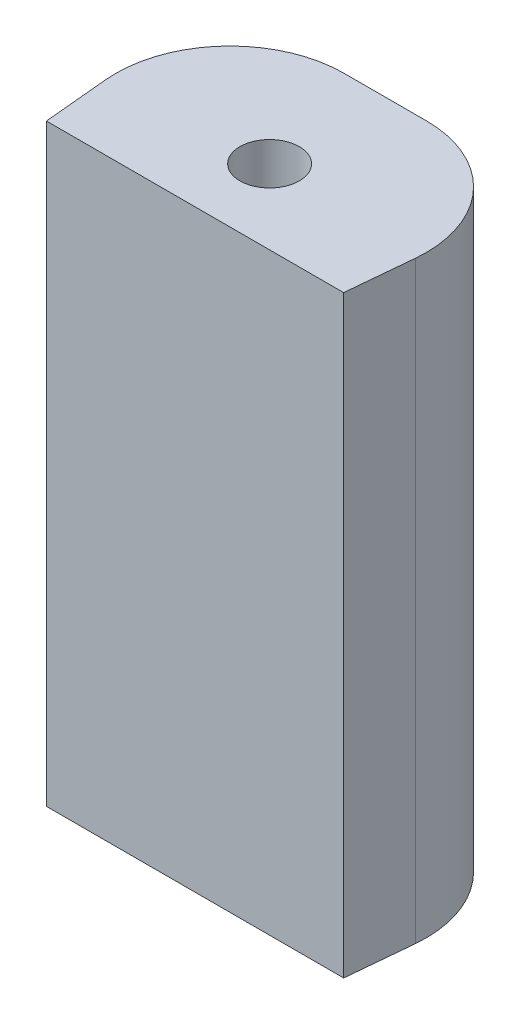
SolidWorks part; units mm, degrees
ref_plane "Front Plane" through (0, 0, 0) normal (0, 0, 1) x (1, 0, 0)
ref_plane "Top Plane" through (0, 0, 0) normal (0, 1, 0) x (1, 0, 0)
ref_plane "Right Plane" through (0, 0, 0) normal (1, 0, 0) x (0, 0, -1)
sketch "Sketch1" plane through (0, 0, 0) normal (0, 1, 0) x (1, 0, 0)
  line L0 (1.1081, 1.7265) -> (-45.0799, 1.7265) construction
  line L1 (-45.0799, 1.7265) -> (-45.0799, -11.2275) construction
  line L2 (-45.0799, -11.2275) -> (43.7517, -11.2275) construction
  line L3 (1.1081, 103.3269) -> (1.1081, -99.8738) construction
  line L4 (-45.0799, -11.2275) -> (-45.0799, -20.7525) construction
  line L5 (-28.2049, 1.7265) -> (-28.2049, -3.6075) construction
  line L6 (-9.9553, -3.6075) -> (-6.7697, -3.6075)
  line L7 (-28.2049, -3.6075) -> (-9.9553, -3.6075) construction
  line L8 (-6.7697, -3.6075) -> (1.1081, -3.6075) construction
  line L9 (8.9859, -3.6075) -> (12.1715, -3.6075)
  line L10 (12.1715, -3.6075) -> (18.1346, -3.6075) construction
  line L11 (12.1715, -3.6075) -> (18.1346, -3.6075) construction
  line L12 (18.1346, -3.6075) -> (29.3788, -3.6075) construction
  line L13 (1.1081, -3.6075) -> (8.9859, -3.6075) construction
  line L14 (-6.7697, -3.6075) -> (8.9859, -3.6075)
  circle A0 centre (1.1081, -11.3265) radius 1.9844 construction
  circle A1 centre (1.1081, -11.3265) radius 1.9844
  spline S0 degree 3 poles (1.1081, -99.8738) (4.5273, -73.5318) (7.9866, -47.1872) (10.6029, -20.7525) knots 0 0 0 0 0.38497 0.38497 0.38497 0.38497
  spline S3 degree 3 poles (1.1081, -99.8738) (-2.3112, -73.5318) (-5.7704, -47.1872) (-8.3867, -20.7525) knots 0 0 0 0 0.38497 0.38497 0.38497 0.38497
  spline S4 degree 3 poles (10.6029, -20.7525) (11.1, -15.7302) (11.6306, -10.016) (12.114, -4.2968) (12.1715, -3.6075) knots 0.38497 0.38497 0.38497 0.38497 0.458109 0.468132 0.468132 0.468132 0.468132
  spline S5 degree 3 poles (-8.3867, -20.7525) (-8.8838, -15.7302) (-9.4144, -10.016) (-9.8978, -4.2968) (-9.9553, -3.6075) knots 0.38497 0.38497 0.38497 0.38497 0.458109 0.468132 0.468132 0.468132 0.468132
  spline S8 degree 3 poles (12.1715, -3.6075) (12.8364, 4.367) (14.1908, 23.6726) (14.0058, 48.0803) (13.0188, 67.5796) (11.3266, 78.9472) (9.5869, 86.9693) (8.1237, 93.6397) (6.4505, 97.563) (4.8164, 101.3994) (2.3437, 102.5279) (1.1081, 103.3269) knots 0.468132 0.468132 0.468132 0.468132 0.584075 0.748482 0.821537 0.866809 0.914778 0.94069 0.965303 0.976863 1 1 1 1 construction
  spline S9 degree 3 poles (1.1081, 99.6196) (1.2739, 99.518) (1.6209, 99.2976) (2.0134, 99.0137) (2.3095, 98.7539) (2.4667, 98.5788) (2.6076, 98.3713) (2.8163, 97.9774) (3.0534, 97.4394) (3.4327, 96.5453) (3.8774, 95.496) (4.541, 93.8448) (5.2023, 91.9048) (5.8236, 89.3366) (6.4213, 86.5662) (7.0145, 83.8293) (7.767, 80.1951) (8.6007, 75.6781) (9.6391, 68.4081) (10.3034, 59.2354) (10.6788, 47.9926) (10.8555, 36.7918) (10.7415, 25.5951) (10.3009, 14.4244) (9.6564, 4.6878) (9.1767, -1.3266) (8.9859, -3.6075) knots 0.118744 0.118744 0.118744 0.118744 0.122149 0.125554 0.12896 0.132365 0.13577 0.139175 0.142581 0.145986 0.152796 0.159607 0.173228 0.186849 0.20047 0.214091 0.227711 0.254953 0.282195 0.336679 0.391163 0.445646 0.50013 0.554614 0.609098 0.642376 0.642376 0.642376 0.642376 construction
  spline S10 degree 3 poles (-7.1984, 1.7265) (-7.237, 2.2289) (-7.5577, 6.4638) (-8.0847, 14.4244) (-8.5253, 25.5951) (-8.6393, 36.7918) (-8.4626, 47.9926) (-8.0872, 59.2354) (-7.4229, 68.4081) (-6.3845, 75.6781) (-5.5508, 80.1951) (-4.7983, 83.8293) (-4.2051, 86.5662) (-3.6074, 89.3366) (-2.9861, 91.9048) (-2.3248, 93.8448) (-1.6612, 95.496) (-1.2165, 96.5453) (-0.8372, 97.4394) (-0.6001, 97.9774) (-0.3914, 98.3713) (-0.2505, 98.5788) (-0.0933, 98.7539) (0.2028, 99.0137) (0.5953, 99.2976) (0.9423, 99.518) (1.1081, 99.6196) knots 0.492798 0.492798 0.492798 0.492798 0.50013 0.554614 0.609098 0.663581 0.718065 0.772549 0.827033 0.854275 0.881516 0.895137 0.908758 0.922379 0.936 0.949621 0.956432 0.963242 0.966647 0.970053 0.973458 0.976863 0.980268 0.983674 0.987079 0.990484 0.990484 0.990484 0.990484 construction
  spline S11 degree 3 poles (-10.3826, 1.7265) (-10.8572, 7.9268) (-11.9611, 25.4575) (-11.7896, 48.0803) (-10.8026, 67.5796) (-9.1104, 78.9472) (-7.3707, 86.9693) (-5.9075, 93.6397) (-4.2343, 97.563) (-2.6002, 101.3994) (-0.1276, 102.5279) (1.1081, 103.3269) knots 0.493976 0.493976 0.493976 0.493976 0.584075 0.748482 0.821537 0.866809 0.914778 0.94069 0.965303 0.976863 1 1 1 1 construction
  spline S12 degree 3 poles (-9.9553, -3.6075) (-10.1035, -1.8299) (-10.2465, -0.0519) (-10.3826, 1.7265) knots 0.468132 0.468132 0.468132 0.468132 0.493976 0.493976 0.493976 0.493976 construction
  spline S13 degree 3 poles (-6.7697, -3.6075) (-6.9185, -1.8292) (-7.0618, -0.0511) (-7.1984, 1.7265) knots 0.466852 0.466852 0.466852 0.466852 0.492798 0.492798 0.492798 0.492798 construction
  dimension "D4" = 3.9688
  dimension "D1" = 12.954
  dimension "D2" = 9.525
  dimension "D3" = 5.334
extrude "Boss-Extrude1" add sketch "Sketch1" along normal blind 169.8727
sketch "Sketch2" plane through (0, 169.8727, 0) normal (0, 1, 0) x (1, 0, 0)
  line L1 (-9.9553, -3.6075) -> (25.8085, -3.6075)
  line L2 (-9.9553, -3.6075) -> (-9.9553, -26.3125)
  line L3 (-9.9553, -26.3125) -> (25.8085, -26.3125)
  line L4 (25.8085, -3.6075) -> (25.8085, -26.3125)
  circle A0 centre (1.1081, -11.3265) radius 1.9844 construction
  dimension "D1" = 14.986
extrude "Cut-Extrude1" cut sketch "Sketch2" against normal blind 23.0581
extrude "Cut-Extrude2" cut sketch "Sketch2<2>" along normal blind 23.0581 from surface starting at face at (-1.1046, 0, 29.7187)
sketch "Sketch2<2>" plane through (0, 169.8727, 0) normal (0, 1, 0) x (1, 0, 0) same geometry as "Sketch2"
fillet "Fillet1" radius 7.62 6 edges at (-7.8242, 11.5291, 26.3125) (10.0403, 11.5291, 26.3125) (12.1715, 84.9363, 3.6075) (-7.8242, 158.3436, 26.3125) (10.0403, 158.3436, 26.3125)
sketch "Sketch6" plane through (0, 0, 0) normal (0, -1, 0) x (1, 0, 0)
  line L0 (1.1081, 3.6075) -> (1.1081, 99.8738) construction
  line L1 (-1.6395, 3.6075) -> (3.8557, 3.6075) construction
  line L2 (-6.9254, 34.7606) -> (9.1416, 34.7606) construction
  circle A0 centre (1.1081, 71.9338) radius 2.1
  circle A1 centre (1.1081, 34.7606) radius 2.1
  dimension "D1" = 4.2
  dimension "D2" = 27.94
extrude "Cut-Extrude3" cut sketch "Sketch6" against normal through all both and the other way through all
sketch "Sketch7" plane through (0, 0, 0) normal (1, 0, 0) x (0, 0, -1)
  line L0 (-3.6075, 146.8145) -> (-3.6075, 23.0581) construction
  line L1 (-99.8738, 0) -> (-3.6075, 0)
  line L2 (-99.8738, 0) -> (-99.8738, 79.911)
  line L3 (-99.8738, 79.911) -> (-3.6075, 79.911)
  line L4 (-3.6075, 0) -> (-3.6075, 79.911)
  line L6 (-99.8738, 169.8727) -> (-3.6075, 169.8727)
  line L7 (-99.8738, 169.8727) -> (-99.8738, 119.5579)
  line L8 (-99.8738, 119.5579) -> (-3.6075, 119.5579)
  line L9 (-3.6075, 169.8727) -> (-3.6075, 119.5579)
  dimension "D2" = 39.6469
extrude "Cut-Extrude4" cut sketch "Sketch7" against normal through all both and the other way through all
sketch "Sketch8" plane through (0, 79.911, 0) normal (0, -1, 0) x (1, 0, 0)
  line L1 (-35.7382, 136.6065) -> (32.4462, 136.6065)
  line L2 (-35.7382, 136.6065) -> (-35.7382, 16.3075)
  line L3 (-35.7382, 16.3075) -> (32.4462, 16.3075)
  line L4 (32.4462, 136.6065) -> (32.4462, 16.3075)
  dimension "D1" = 12.7
extrude "Cut-Extrude5" cut sketch "Sketch8" against normal through all both
